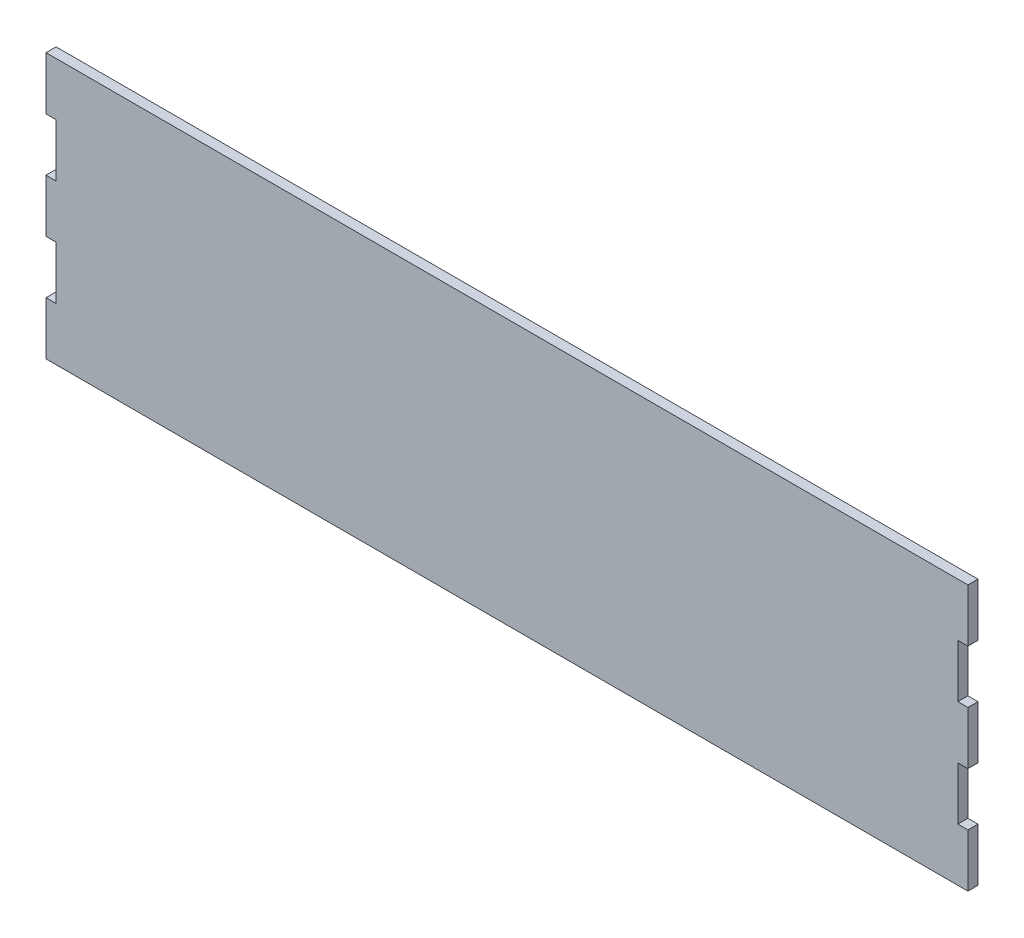
SolidWorks part; units mm, degrees
material "1060 Alloy"
ref_plane "Front Plane" through (0, 0, 0) normal (0, 0, 1) x (1, 0, 0)
ref_plane "Top Plane" through (0, 0, 0) normal (0, 1, 0) x (1, 0, 0)
ref_plane "Right Plane" through (0, 0, 0) normal (1, 0, 0) x (0, 0, -1)
sketch "Sketch1" plane through (0, 0, 0) normal (0, 0, 1) x (1, 0, 0)
  line L0 (95.25, 50.8) -> (95.25, 25.4)
  line L1 (0, 0) -> (622.3, 0) construction
  line L2 (0, 0) -> (0, 127) construction
  line L3 (0, 127) -> (622.3, 127) construction
  line L4 (622.3, 0) -> (622.3, 127) construction
  line L5 (90.424, 127) -> (531.876, 127)
  line L6 (95.25, 101.6) -> (95.25, 76.2)
  line L7 (95.25, 0) -> (527.05, 0)
  line L8 (527.05, 101.6) -> (527.05, 76.2)
  line L10 (90.424, 127) -> (90.424, 101.6)
  line L11 (90.424, 101.6) -> (95.25, 101.6)
  line L12 (527.05, 50.8) -> (527.05, 25.4)
  line L13 (95.25, 76.2) -> (90.424, 76.2)
  line L15 (95.25, 50.8) -> (90.424, 50.8)
  line L16 (90.424, 76.2) -> (90.424, 50.8)
  line L17 (90.424, 25.4) -> (95.25, 25.4)
  line L18 (90.424, 25.4) -> (90.424, 0)
  line L19 (90.424, 0) -> (95.25, 0)
  line L21 (527.05, 101.6) -> (531.876, 101.6)
  line L22 (531.876, 127) -> (531.876, 101.6)
  line L23 (527.05, 76.2) -> (531.876, 76.2)
  line L25 (527.05, 50.8) -> (531.876, 50.8)
  line L26 (531.876, 76.2) -> (531.876, 50.8)
  line L27 (527.05, 25.4) -> (531.876, 25.4)
  line L29 (527.05, 0) -> (531.876, 0)
  line L30 (531.876, 25.4) -> (531.876, 0)
  dimension "D1" = 127
  dimension "D2" = 622.3
  dimension "D3" = 95.25
  dimension "D4" = 95.25
  dimension "D5" = 4.826
extrude "Boss-Extrude1" add sketch "Sketch1" along normal blind 4.826
equation "\"sheet width\"= .19"
equation "\"width\"= 24.5"
equation "\"length\"= 34.5"
equation "\"standoff hole size\"= .5"
equation "\"ground clearence\"= 3"
equation "\"small drive pulley\"= 74.55mm"
equation "\"large drive pulley\"= 150.95mm"
equation "\"drive axle hole size\"= .5"
equation "\"front pulley clearence\"= 1"
equation "\"center support location\"= 19"
equation "\"inner to outer wall size\"= 3.75"
equation "\"D2@Sketch1\"=\"width\""
equation "\"D3@Sketch1\"=\"inner to outer wall size\""
equation "\"D4@Sketch1\"=\"inner to outer wall size\""
equation "\"D5@Sketch1\"=\"sheet width\""
equation "\"D1@Boss-Extrude1\"=\"sheet width\""
